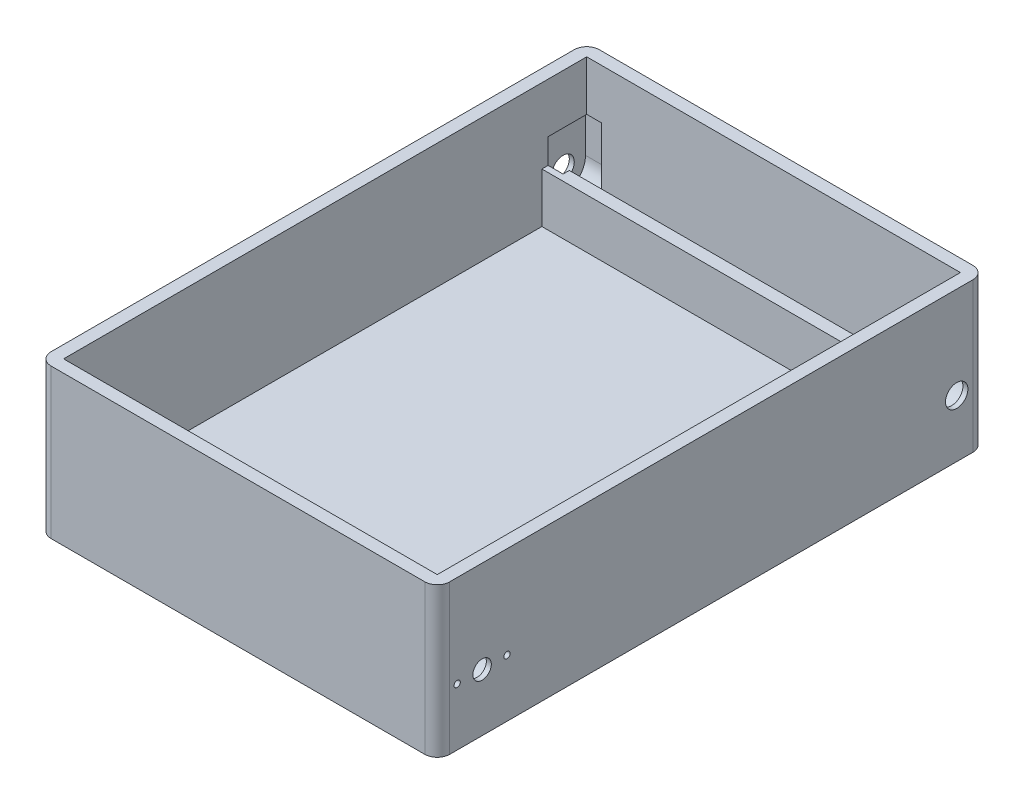
SolidWorks part; units mm, degrees
ref_plane "Front Plane" through (0, 0, 0) normal (0, 0, 1) x (1, 0, 0)
ref_plane "Top Plane" through (0, 0, 0) normal (0, 1, 0) x (1, 0, 0)
ref_plane "Right Plane" through (0, 0, 0) normal (1, 0, 0) x (0, 0, -1)
sketch "Main Body" plane through (0, 0, 0) normal (0, 1, 0) x (1, 0, 0)
  line L0 (-75, 110) -> (75, 110)
  line L1 (-75, -105) -> (75, -105)
  line L2 (-75, -105) -> (-75, 105)
  line L3 (-75, 105) -> (75, 105)
  line L4 (75, -105) -> (75, 105)
  line L5 (-75, -105) -> (75, 105) construction
  line L6 (-75, 105) -> (75, -105) construction
  line L7 (80, -105) -> (80, 105)
  line L8 (-75, -110) -> (75, -110)
  line L9 (-80, -105) -> (-80, 105)
  line L10 (-80, -110) -> (80, -110) construction
  line L11 (-80, -110) -> (-80, 110) construction
  line L12 (80, -110) -> (80, 110) construction
  line L13 (-80, 110) -> (80, 110) construction
  arc A0 (-75, -110) -> (-80, -105) centre (-75, -105) cw
  arc A1 (80, -105) -> (75, -110) centre (75, -105) cw
  arc A2 (75, 110) -> (80, 105) centre (75, 105) cw
  arc A3 (-75, 110) -> (-80, 105) centre (-75, 105) ccw
  point P0 (0, 0)
  dimension "D4" = 5
  dimension "D1" = 75
  dimension "D2" = 210
  dimension "D3" = 5
extrude "Boss-Extrude1" add sketch "Main Body" along normal blind 10 contours L1 L4 L3 L2 | L9 L8 L7 L0 L4 L1 L2 L3 region at (0, 0, -107.2797) region at (0, 0, 0)
extrude "Boss-Extrude3" add sketch "Main Body<4>" along normal blind 50 from surface starting at face at (0, 10, 0)
sketch "Main Body<4>" plane through (0, 0, 0) normal (0, 1, 0) x (1, 0, 0) same geometry as "Main Body"
sketch "Sketch1" plane through (75, 0, 0) normal (-1, 0, 0) x (0, 0, 1)
  line L0 (105, 60) -> (105, 10) construction
  line L1 (-105, 10) -> (105, 10) construction
  line L2 (79, 17.5) -> (105, 17.5)
  line L3 (79, 10) -> (105, 10)
  line L4 (79, 10) -> (79, 36)
  line L5 (79, 36) -> (105, 36)
  line L6 (105, 10) -> (105, 36)
  line L7 (79, 10) -> (105, 36) construction
  line L8 (79, 36) -> (105, 10) construction
  circle A0 centre (92, 23) radius 13
  line M2 (-105, 10) -> (105, 10)
  line M3 (105, 10) -> (105, 60)
  dimension "D1" = 26
  dimension "D2" = 7.5
extrude "Boss-Extrude4" add sketch "Sketch1" along normal up to surface (150 mm away) contours A0 L4 M2 | A0 L3 M3 region at (75, 12.5201, 82.0674) region at (75, 12.5201, 101.9326) up to face at (-75, 35, 0)
sketch "Sketch2" plane through (0, 0, 0) normal (1, 0, 0) x (0, 0, -1)
  line L0 (-105, 60) -> (-105, 17.5) construction
  line L1 (-105, 10) -> (-79, 10)
  line L2 (-105, 10) -> (-105, 17.5)
  line L3 (-105, 17.5) -> (-79, 17.5)
  line L4 (-79, 10) -> (-79, 17.5)
  line L5 (105, 10) -> (-79, 10) construction
  line L6 (-79, 10) -> (-79, 17.5) construction
  line L7 (-79, 17.5) -> (-80.2208, 17.5) construction
extrude "Cut-Extrude1" cut sketch "Sketch2" against normal mid plane 12
sketch "Sketch3" plane through (0, 10, 0) normal (0, 1, 0) x (1, 0, 0)
  line L0 (75, -105) -> (-75, -105) construction
  line L1 (-6, -79) -> (-11, -79)
  line L2 (-6, -79) -> (-6, -105)
  line L3 (-6, -105) -> (-11, -105)
  line L4 (-11, -79) -> (-11, -105)
  line L5 (0, 0) -> (0, -105) construction
  line L6 (-75, -79) -> (-6, -79) construction
  line L7 (11, -79) -> (11, -105)
  line L8 (6, -105) -> (11, -105)
  line L9 (6, -79) -> (6, -105)
  line L10 (6, -79) -> (11, -79)
  dimension "D1" = 5
extrude "Boss-Extrude5" add sketch "Sketch3" along normal up to surface (7.5 mm away) up to face at (40.5, 17.5, 79.6104)
sketch "Sketch4" plane through (0, 10, 0) normal (0, 1, 0) x (1, 0, 0)
  line L0 (-75, -105) -> (-75, 105) construction
  line L1 (-75, 92) -> (75, 92)
  line L2 (-75, 92) -> (-75, 87)
  line L3 (-75, 87) -> (75, 87)
  line L4 (75, 92) -> (75, 87)
  line L5 (75, 105) -> (75, -105) construction
  line L6 (-75, 105) -> (75, 105) construction
  point P10 (75, 91.3674)
  dimension "D1" = 18
  dimension "D2" = 5
extrude "Boss-Extrude6" add sketch "Sketch4" along normal blind 20
sketch "Sketch5" plane through (80, 0, 0) normal (1, 0, 0) x (0, 0, -1)
  circle A0 centre (-92, 23) radius 3.5 construction
  circle A1 centre (-92, 23) radius 3.5
  circle A2 centre (-92, 23) radius 3.7
  dimension "D1" = 0.2
extrude "Cut-Extrude4" cut sketch "Sketch5" against normal up to next contours A1 | A2 A1 region at (80, 23, 92) region at (80, 23, 95.5953)
sketch "Sketch6" plane through (-75, 0, 0) normal (1, 0, 0) x (0, 0, -1)
  circle A0 centre (-92, 23) radius 13
  dimension "D1" = 26
extrude "Cut-Extrude5" cut sketch "Sketch6" against normal offset from surface (3 mm away) 2 up to face at (-80, 30, 0)
mirror "Mirror1" about plane through (0, 0, 0) normal (1, 0, 0) of "Cut-Extrude4"
sketch "Sketch8" plane through (75, 0, 0) normal (-1, 0, 0) x (0, 0, 1)
  circle A0 centre (92, 23) radius 13
  dimension "D1" = 26
extrude "Cut-Extrude6" cut sketch "Sketch8" against normal offset from surface (3 mm away) 2 up to face at (80, 23, 88.3)
sketch "Sketch10" plane through (80, 0, 0) normal (1, 0, 0) x (0, 0, -1)
  circle A1 centre (-82, 23) radius 1.25
  circle A2 centre (-82, 23) radius 1.25
  circle A3 centre (-102, 23) radius 1.25
  circle A4 centre (-102, 23) radius 1.25
  circle A5 centre (-92, 23) radius 12.5
  circle A6 centre (-92, 23) radius 12.5
  dimension "D1" = 0
  dimension "D2" = 0
  dimension "D3" = 0
extrude "Cut-Extrude7" cut sketch "Sketch10" against normal up to next contours A2 | A4 region at (80, 23, 82) region at (80, 23, 102)
mirror "Mirror3" about plane through (0, 0, 0) normal (1, 0, 0) of "Cut-Extrude7"
sketch "Sketch11" plane through (80, 0, 0) normal (1, 0, 0) x (0, 0, -1)
  circle A0 centre (98.5, 23) radius 4.5 construction
  circle A1 centre (98.5, 23) radius 4.5
  circle A2 centre (98.5, 23) radius 8.55
  dimension "D1" = 17.1
extrude "Cut-Extrude10" cut sketch "Sketch11" against normal through all contours A1 region at (80, 23, -98.5)
sketch "Sketch12" plane through (75, 0, 0) normal (-1, 0, 0) x (0, 0, 1)
  circle A0 centre (-98.5, 23) radius 9
  dimension "D1" = 18
extrude "Cut-Extrude11" cut sketch "Sketch12" against normal blind 3
extrude "Cut-Extrude12" cut sketch "Sketch12<3>" along normal blind 6
sketch "Sketch12<3>" plane through (75, 0, 0) normal (-1, 0, 0) x (0, 0, 1) same geometry as "Sketch12"
sketch "Sketch13" plane through (75, 0, 0) normal (-1, 0, 0) x (0, 0, 1)
  line L3 (-92, 10) -> (-92, 16.7751)
  line L4 (-105, 16.7751) -> (-105, 10)
  line L5 (-105, 10) -> (-92, 10)
  line L6 (-92, 10) -> (-92, 16.7751)
  line L7 (-105, 16.7751) -> (-105, 10)
  line L8 (-105, 10) -> (-92, 10)
  arc A1 (-105, 16.7751) -> (-92, 16.7751) centre (-98.5, 23) ccw
  arc A2 (-105, 16.7751) -> (-92, 16.7751) centre (-98.5, 23) ccw
  dimension "D1" = 0
extrude "Boss-Extrude7" add sketch "Sketch13" along normal up to surface (6 mm away) up to face at (69, 23, -106.25)
ref_axis "Axis1" through (78, 23, -98.5) along (1, 0, 0)
ref_plane "Plane1" through (0, 23, 0) normal (0, 1, 0) x (1, 0, 0)
sketch "Sketch14" plane through (0, 23, 0) normal (0, 1, 0) x (1, 0, 0)
  line L0 (75, 105) -> (75, 92) construction
  line L1 (69, 105) -> (69, 92) construction
  line L2 (69, 107.5) -> (78, 107.5)
  line L3 (69, 107.5) -> (69, 89.5)
  line L4 (69, 89.5) -> (78, 89.5)
  line L5 (78, 107.5) -> (78, 89.5)
  line L6 (80, 105) -> (80, -105) construction
  line L7 (78, 107.5) -> (69, 107.5) construction
  point P6 (69, 98.5)
  point P7 (69, 98.5)
  point P8 (78.3426, 105)
  point P13 (67.1638, 107.5)
  dimension "D1" = 2
  dimension "D2" = 6
extrude "Cut-Extrude13" cut sketch "Sketch14" along normal offset from surface (17 mm away) 10 up to face at (0, 30, -89.5) offset beyond the face yes
mirror "Mirror8" about plane through (0, 0, 0) normal (1, 0, 0) of "Cut-Extrude13", "Boss-Extrude7", "Cut-Extrude12", "Cut-Extrude11"
